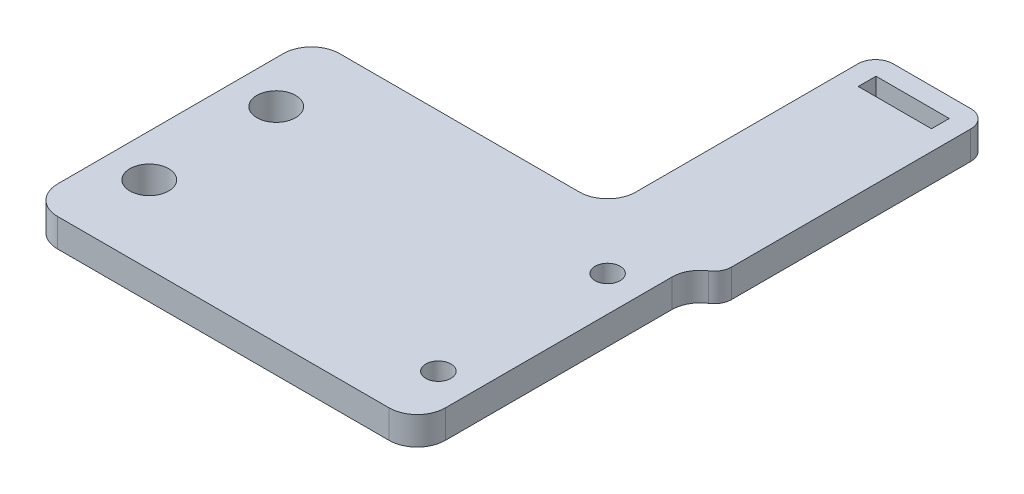
SolidWorks part; units mm, degrees
ref_plane "Front" through (0, 0, 0) normal (0, 0, 1) x (1, 0, 0)
ref_plane "Top" through (0, 0, 0) normal (0, 1, 0) x (1, 0, 0)
ref_plane "Right" through (0, 0, 0) normal (1, 0, 0) x (0, 0, -1)
sketch "Sketch1" plane through (0, 0, 0) normal (0, 1, 0) x (1, 0, 0)
  line L1 (0, 0) -> (34.925, 0)
  line L2 (0, 0) -> (0, 25.4)
  line L3 (0, 25.4) -> (34.925, 25.4)
  line L4 (34.925, 0) -> (34.925, 25.4)
  dimension "D1" = 25.4
  dimension "D2" = 34.925
extrude "Boss-Extrude1" add sketch "Sketch1" along normal blind 2.54
sketch "Sketch2" plane through (0, 2.54, 0) normal (0, 1, 0) x (1, 0, 0)
  line L0 (0, 12.7) -> (34.925, 12.7) construction
  line L1 (0, 25.4) -> (0, 0) construction
  line L2 (34.925, 0) -> (34.925, 25.4) construction
  circle A0 centre (3.81, 18.415) radius 1.7462
  circle A1 centre (3.81, 6.985) radius 1.7463
  dimension "D1" = 3.4925
  dimension "D2" = 5.715
  dimension "D3" = 3.81
extrude "Cut-Extrude3" cut sketch "Sketch2" along normal through all and the other way through all
sketch "Sketch5" plane through (0, 2.54, 0) normal (0, 1, 0) x (1, 0, 0)
  line L0 (0, 12.7) -> (34.925, 12.7) construction
  line L1 (0, 25.4) -> (0, 0) construction
  line L2 (34.925, 0) -> (34.925, 25.4) construction
  line L3 (34.925, 25.4) -> (0, 25.4) construction
  circle A0 centre (31.75, 20.32) radius 1.1303
  circle A1 centre (31.75, 5.08) radius 1.1303
  dimension "D1" = 2.2606
  dimension "D2" = 5.08
  dimension "D3" = 3.175
extrude "Cut-Extrude4" cut sketch "Sketch5" against normal through all
sketch "Sketch6" plane through (0, 2.54, 0) normal (0, 1, 0) x (1, 0, 0)
  line L0 (31.75, 20.32) -> (31.75, 5.08) construction
  line L1 (31.75, 20.32) -> (31.75, 38.7587) construction
  line L2 (34.925, 25.4) -> (0, 25.4) construction
  line L3 (36.83, 49.53) -> (26.67, 49.53)
  line L4 (36.83, 49.53) -> (36.83, 25.4)
  line L5 (36.83, 25.4) -> (26.67, 25.4)
  line L6 (26.67, 49.53) -> (26.67, 25.4)
  line L7 (36.83, 49.53) -> (26.67, 25.4) construction
  line L8 (36.83, 25.4) -> (26.67, 49.53) construction
  point P5 (31.75, 37.465)
  point P12 (31.75, 12.7)
  dimension "D1" = 36.83
  dimension "D2" = 10.16
extrude "Boss-Extrude2" add sketch "Sketch6" against normal blind 2.54
fillet "Fillet1" radius 2.54 2 edges at (34.925, 1.27, -25.4) (26.67, 1.27, -25.4)
fillet "Fillet2" radius 1.5875 3 edges at (36.83, 1.27, -49.53) (26.67, 1.27, -49.53) (36.83, 1.27, -25.4)
fillet "Fillet3" radius 2.54 3 edges at (0, 1.27, 0) (0, 1.27, -25.4) (34.925, 1.27, 0)
sketch "Sketch8" plane through (0, 2.54, 0) normal (0, 1, 0) x (1, 0, 0)
  line L0 (31.75, 5.08) -> (31.75, 20.3549) construction
  line L1 (31.75, 20.3549) -> (31.75, 49.53) construction
  line L2 (35.2425, 49.53) -> (28.2575, 49.53) construction
  line L4 (28.4514, 47.7901) -> (35.0486, 47.7901)
  line L5 (28.4514, 47.7901) -> (28.4514, 46.1899)
  line L6 (28.4514, 46.1899) -> (35.0486, 46.1899)
  line L7 (35.0486, 47.7901) -> (35.0486, 46.1899)
  line L8 (28.4514, 47.7901) -> (35.0486, 46.1899) construction
  line L9 (28.4514, 46.1899) -> (35.0486, 47.7901) construction
  point P3 (31.75, 46.99)
  dimension "D1" = 1.6002
  dimension "D2" = 6.5973
  dimension "D3" = 2.54
extrude "Cut-Extrude6" cut sketch "Sketch8" against normal blind 2.54
